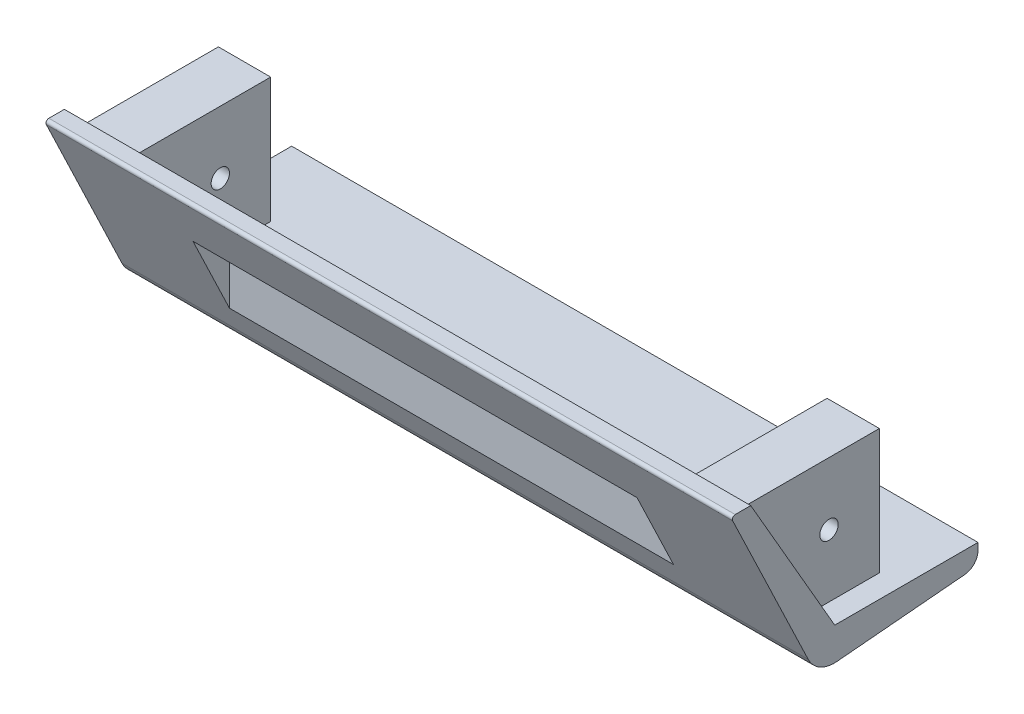
SolidWorks part; units mm, degrees
ref_plane "Front Plane" through (0, 0, 0) normal (0, 0, 1) x (1, 0, 0)
ref_plane "Top Plane" through (0, 0, 0) normal (0, 1, 0) x (1, 0, 0)
ref_plane "Right Plane" through (0, 0, 0) normal (1, 0, 0) x (0, 0, -1)
sketch "Sketch1" plane through (0, 0, 0) normal (1, 0, 0) x (0, 0, -1)
  line L0 (0, 0) -> (-29.3294, 50.8)
  line L1 (0, 0) -> (50, 0)
  line L2 (-29.3294, 50.8) -> (-36.3294, 50.8)
  line L3 (-36.3294, 50.8) -> (-6.2529, -12)
  line L4 (-6.2529, -12) -> (50, -7)
  line L5 (50, -7) -> (50, 0)
  line L6 (-6.2529, -12) -> (-6.2529, 0) construction
  line L7 (-12, 0) -> (0, 0) construction
  dimension "D1" = 50
  dimension "D2" = 60
  dimension "D3" = 50.8
  dimension "D4" = 7
  dimension "D5" = 7
  dimension "D6" = 12
extrude "Boss-Extrude2" add sketch "Sketch1" along normal mid plane 239.55
sketch "Sketch2" plane through (0, 0, 0) normal (0, 0, 1) x (1, 0, 0)
  line L0 (0, 0) -> (0, 50.8) construction
  line L5 (115.75, 47.625) -> (96.7, 47.625) construction
  line L6 (115.75, 47.625) -> (115.75, 3.175) construction
  line L11 (115.75, 3.175) -> (96.7, 3.175) construction
  line L12 (96.7, 47.625) -> (96.7, 3.175) construction
  line L14 (115.35, 47.225) -> (115.35, 3.575)
  line L15 (115.35, 3.575) -> (97.1, 3.575)
  line L28 (97.1, 47.225) -> (97.1, 3.575)
  line L29 (115.35, 47.225) -> (97.1, 47.225)
  line L30 (-96.7, 47.625) -> (-96.7, 3.175) construction
  line L31 (-115.75, 3.175) -> (-96.7, 3.175) construction
  line L32 (-115.75, 47.625) -> (-115.75, 3.175) construction
  line L33 (-115.75, 47.625) -> (-96.7, 47.625) construction
  line L34 (-115.35, 47.225) -> (-97.1, 47.225)
  line L35 (-97.1, 47.225) -> (-97.1, 3.575)
  line L36 (-115.35, 3.575) -> (-97.1, 3.575)
  line L37 (-115.35, 47.225) -> (-115.35, 3.575)
  line L39 (119.775, 0) -> (-119.775, 0) construction
  line L40 (119.775, 50.8) -> (-119.775, 50.8) construction
  line L41 (119.775, 0) -> (119.775, 50.8) construction
  dimension "D2" = 19.05
  dimension "D3" = 44.45
  dimension "D6" = 3.175
  dimension "D4" = 3.175
  dimension "D7" = 4.025
  dimension "D1" = 193.4
  dimension "D5" = 0.4
extrude "Boss-Extrude1" add sketch "Sketch2" along normal up to surface and the other way blind 20 up to face at (0, 25.4, 14.6647)
sketch "Sketch4" plane through (0, 0, 0) normal (1, 0, 0) x (0, 0, -1)
  line L1 (-26.7297, 30.7556) -> (-20, 34.641)
  line L2 (-36.3294, 50.8) -> (-6.2529, -12) construction
  line L3 (0, 0) -> (-29.3294, 50.8) construction
  line L4 (-20, 34.641) -> (-14, 24.2487)
  line L5 (-14, 24.2487) -> (-14, 4.176)
  line L8 (-26.7297, 30.7556) -> (-14, 4.176)
  dimension "D1" = 12
  dimension "D2" = 14
extrude "Cut-Extrude2" cut sketch "Sketch4" against normal mid plane 155
fillet "Fillet1" radius 10 1 edges at (0, -12, 6.2529)
fillet "Fillet2" radius 5 1 edges at (0, -7, -50)
fillet "Fillet3" radius 1 1 edges at (0, 50.8, 36.3294)
sketch "Sketch8" plane through (77.5, 0, 0) normal (-1, 0, 0) x (0, 0, 1)
  line L0 (20, 34.641) -> (22.5981, 33.141)
  line L1 (20, 34.641) -> (26.7297, 30.7556) construction
  line L2 (22.5981, 33.141) -> (17.5981, 24.4808)
  line L3 (14.866, 23.7487) -> (14, 24.2487)
  line L4 (14, 24.2487) -> (20, 34.641) construction
  line L5 (20, 34.641) -> (14, 24.2487)
  arc A0 (17.5981, 24.4808) -> (14.866, 23.7487) centre (15.866, 25.4808) cw
  dimension "D2" = 2
  dimension "D1" = 3
extrude "Cut-Extrude3" cut sketch "Sketch8" against normal blind 10
hole_wizard "M6 Clearance Hole1" positions "Sketch11" profile "Sketch10" hole size "M6" standard "ANSI Metric" end condition through all
sketch "Sketch11" plane through (115.35, 0, 0) normal (1, 0, 0) x (0, 0, -1)
  point P0 (2.4206, 25.4)
sketch "Sketch10" plane through (115.35, 25.4, -2.4206) normal (0, 1, 0) x (0, 0, -1)
  line L0 (0, 0) -> (0, 235.125)
  line L1 (0, 235.125) -> (3.2, 235.125)
  line L2 (3.2, 235.125) -> (3.2, 0)
  line L5 (3.2, 0) -> (0, 0)
  line L11 (0, -6.35) -> (0, 107.95) construction
  dimension "Thru Hole Dia." = 6.4
  dimension "Thru Hole Depth" = 235.125
equation "\"D1@Sketch2\"=187.05mm+0.25in"
equation "\"RailSpacing\"= 188.75mm"
equation "\"D1@Boss-Extrude2\"=\"RailSpacing\"+2in"
